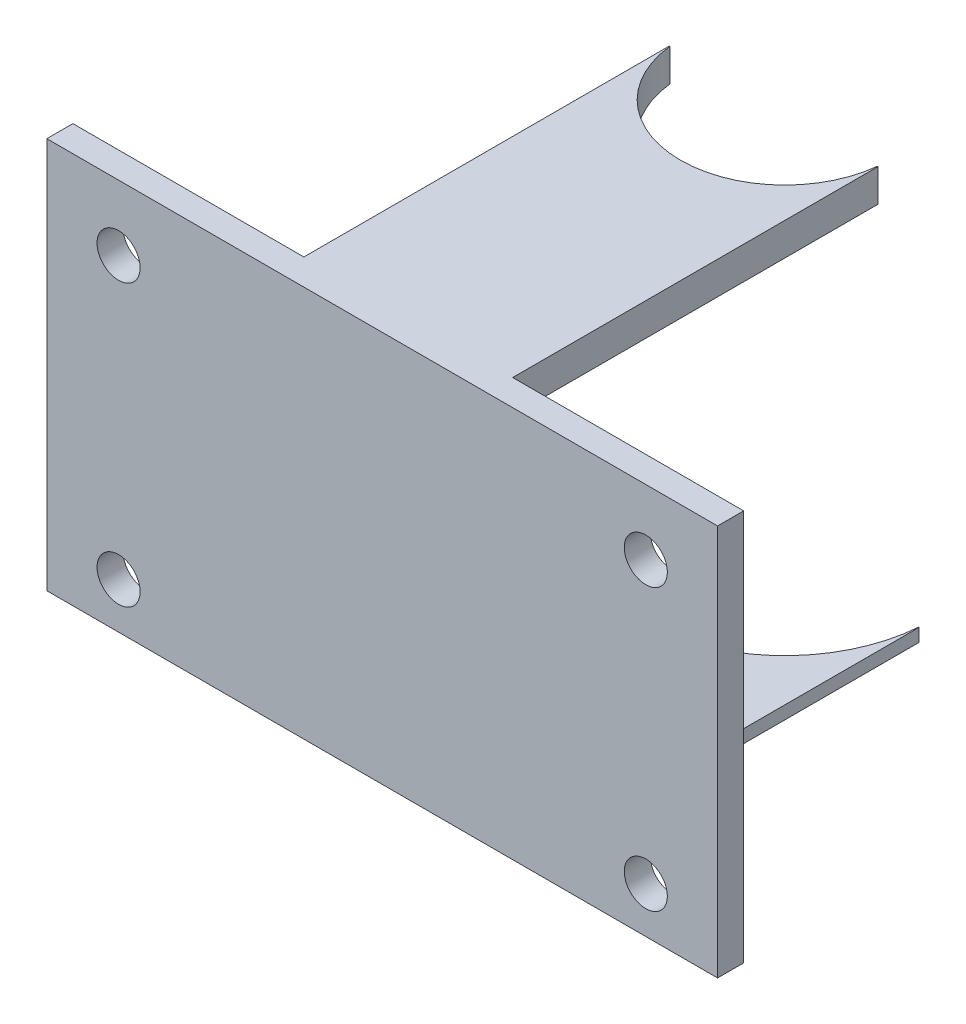
SolidWorks part; units mm, degrees
ref_plane "Front Plane" through (0, 0, 0) normal (0, 0, 1) x (1, 0, 0)
ref_plane "Top Plane" through (0, 0, 0) normal (0, 1, 0) x (1, 0, 0)
ref_plane "Right Plane" through (0, 0, 0) normal (1, 0, 0) x (0, 0, -1)
sketch "Sketch1" plane through (0, 0, 0) normal (0, 0, 1) x (1, 0, 0)
  line L1 (0, 0) -> (51.4, 0)
  line L2 (0, 0) -> (0, 30)
  line L3 (0, 30) -> (51.4, 30)
  line L4 (51.4, 0) -> (51.4, 30)
  dimension "D1" = 51.4
  dimension "D2" = 30
extrude "Boss-Extrude1" add sketch "Sketch1" along normal blind 2
sketch "Sketch2" plane through (0, 0, 0) normal (0, 0, -1) x (-1, 0, 0)
  line L0 (-51.4, 0) -> (-51.4, 30) construction
  line L1 (-5.5, 25) -> (-45.9, 25) construction
  line L2 (-5.5, 25) -> (-5.5, 3.5) construction
  line L3 (-5.5, 3.5) -> (-45.9, 3.5) construction
  line L4 (-45.9, 25) -> (-45.9, 3.5) construction
  line L5 (-5.5, 25) -> (-45.9, 3.5) construction
  line L6 (-5.5, 3.5) -> (-45.9, 25) construction
  line L7 (0, 30) -> (0, 0) construction
  line L8 (0, 0) -> (-51.4, 0) construction
  circle A0 centre (-45.9, 25) radius 1.65
  circle A1 centre (-5.5, 25) radius 1.65
  circle A2 centre (-5.5, 3.5) radius 1.65
  circle A3 centre (-45.9, 3.5) radius 1.65
  point P9 (-25.7, 14.25)
  dimension "D1" = 3.3
  dimension "D2" = 5.5
  dimension "D3" = 5.5
  dimension "D4" = 3.5
  dimension "D5" = 21.5
extrude "Cut-Extrude1" cut sketch "Sketch2" against normal blind 15
sketch "Sketch3" plane through (0, 0, 0) normal (0, 0, -1) x (-1, 0, 0)
  line L5 (-25.7, 30) -> (-25.7, 0) construction
  line L6 (-51.4, 30) -> (0, 30) construction
  line L12 (0, 0) -> (-51.4, 0) construction
  line L14 (-33.7, 27.5) -> (-17.7, 27.5)
  line L15 (-33.7, 27.5) -> (-33.7, 30)
  line L16 (-33.7, 30) -> (-17.7, 30)
  line L17 (-17.7, 27.5) -> (-17.7, 30)
  line L18 (-33.7, 27.5) -> (-17.7, 30) construction
  line L19 (-33.7, 30) -> (-17.7, 27.5) construction
  line L20 (-36.85, 1) -> (-14.55, 1)
  line L21 (-36.85, 1) -> (-36.85, 0)
  line L22 (-36.85, 0) -> (-14.55, 0)
  line L23 (-14.55, 1) -> (-14.55, 0)
  line L24 (-36.85, 1) -> (-14.55, 0) construction
  line L25 (-36.85, 0) -> (-14.55, 1) construction
  point P10 (-25.7, 28.75)
  point P15 (-25.7, 0.5)
  point P16 (0, 0)
  point P17 (0, 0)
  dimension "D1" = 16
  dimension "D2" = 2.5
  dimension "D3" = 22.3
  dimension "D4" = 1
extrude "Boss-Extrude2" add sketch "Sketch3" along normal blind 28
sketch "Sketch4" plane through (0, 30, 0) normal (0, 1, 0) x (1, 0, 0)
  line L0 (51.4, 0) -> (33.7, 0) construction
  line L1 (25.7, 28.85) -> (25.7, -2) construction
  line L3 (51.4, -2) -> (0, -2) construction
  circle A0 centre (25.7, 28.85) radius 8
  point P6 (0, 0)
  point P7 (0, 0)
  point P10 (25.7, 29)
  dimension "D1" = 16
  dimension "D2" = 28.85
extrude "Cut-Extrude3" cut sketch "Sketch4" against normal blind 10
sketch "Sketch6" plane through (0, 1, 0) normal (0, 1, 0) x (1, 0, 0)
  circle A0 centre (25.7, 28.85) radius 11.15
  dimension "D1" = 22.3
extrude "Cut-Extrude4" cut sketch "Sketch6" against normal blind 10
